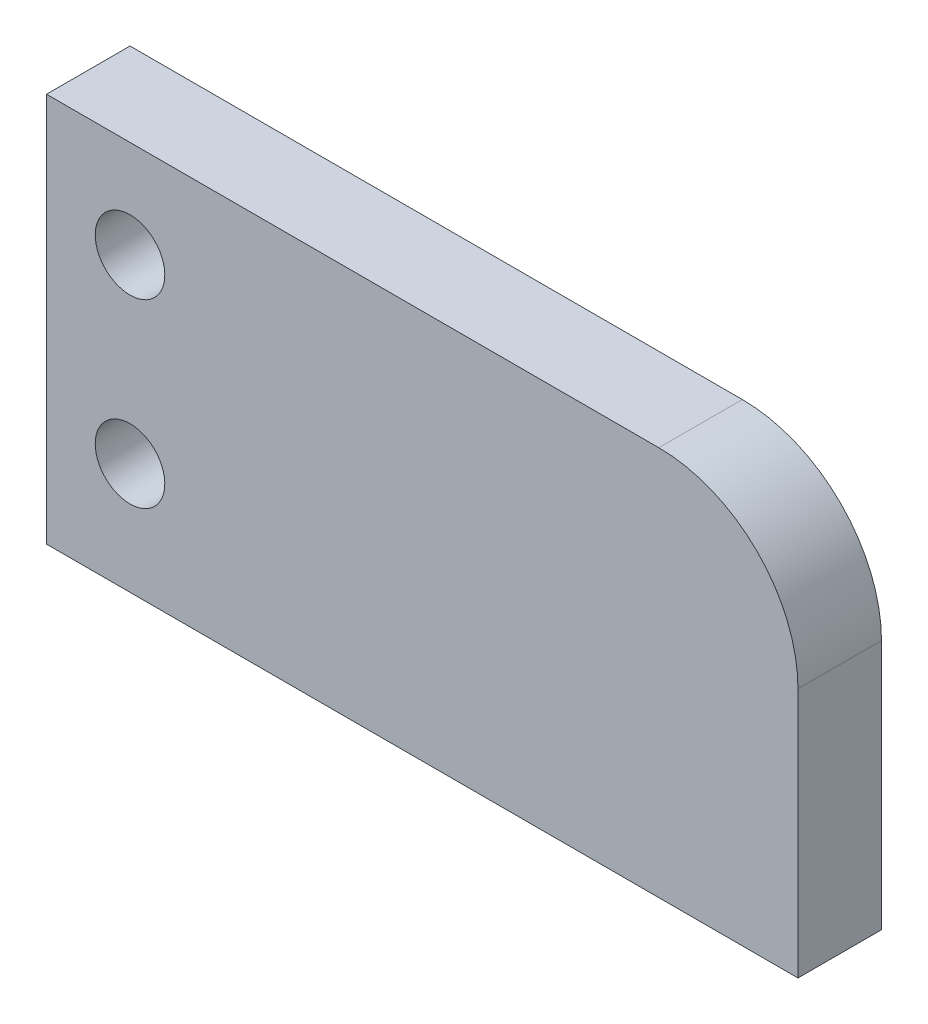
SolidWorks part; units mm, degrees
note: The reader was unsure of these and kept them because the rebuilt part matched: shared geometry of "Sketch2<3>".
ref_plane "Front Plane" through (0, 0, 0) normal (0, 0, 1) x (1, 0, 0)
ref_plane "Top Plane" through (0, 0, 0) normal (0, 1, 0) x (1, 0, 0)
ref_plane "Right Plane" through (0, 0, 0) normal (1, 0, 0) x (0, 0, -1)
sketch "Sketch1" plane through (0, 0, 0) normal (0, 0, 1) x (1, 0, 0)
  line L0 (0, 0) -> (0, 58)
  line L1 (0, 58) -> (19, 58)
  line L2 (19, 58) -> (19, 0)
  line L3 (19, 0) -> (0, 0)
  dimension "D1" = 58
  dimension "D2" = 19
extrude "Boss-Extrude1" add sketch "Sketch1" along normal blind 54
sketch "Sketch2" plane through (0, 0, 0) normal (-1, 0, 0) x (0, 0, 1)
  line L0 (0, 29) -> (27.5, 29)
  line L1 (0, 58) -> (0, 0) construction
  line L2 (27.5, 29) -> (54, 29)
  line L3 (54, 58) -> (54, 0) construction
  circle A0 centre (9.25, 29) radius 1.9
  circle A1 centre (45.75, 29) radius 1.9
  circle A2 centre (27.5, 29) radius 20
  circle A3 centre (27.5, 29) radius 15.5
  dimension "D4" = 3.8
  dimension "D5" = 3.8
  dimension "D6" = 31
  dimension "D7" = 40
  dimension "D1" = 27.5
  dimension "D2" = 18.25
  dimension "D3" = 18.25
extrude "Boss-Extrude2" add sketch "Sketch2<3>" against normal blind 50 contours A3 L0 A0 A2 A1 L2 | A1 A2 L2 | L2 A2 A1 | A3 L2 A1 A2 A0 L0 | A0 A2 L0 | L0 A2 A0
sketch "Sketch2<3>" plane through (0, 0, 0) normal (-1, 0, 0) x (0, 0, 1) same geometry as "Sketch2"
extrude "Cut-Extrude1" cut sketch "Sketch2" against normal blind 10 contours L0 A0 | L0 A0 | L2 A1 | L2 A1 | A2 L0 A0 | A2 A0 L0 | A2 A1 L2 | A2 L2 A1
fillet "Fillet1" radius 10 1 edges at (9.5, 0, 0)
sketch "Sketch3" plane through (0, 0, 0) normal (1, 0, 0) x (0, 0, -1)
  line L0 (0, 0) -> (0, 57)
  line L1 (0, 57) -> (0, 67)
  line L2 (0, 67) -> (-5, 67)
  line L3 (-5, 67) -> (-5, 0)
  line L4 (-54, 0) -> (-10, 0) construction
  line L5 (-5, 0) -> (0, 0)
  dimension "D1" = 57
  dimension "D2" = 5
  dimension "D3" = 10
extrude "Boss-Extrude3" add sketch "Sketch3" against normal blind 50
sketch "Sketch4" plane through (0, 0, 0) normal (0, 0, -1) x (-1, 0, 0)
  line L0 (0, 0) -> (0, 57)
  line L1 (0, 67) -> (0, 0) construction
  line L2 (0, 57) -> (14, 57)
  line L3 (0, 53) -> (50, 53)
  line L4 (50, 0) -> (50, 67) construction
  line L5 (50, 53) -> (50, 0)
  line L6 (50, 0) -> (0, 0)
  line L7 (17, 53) -> (17, 67)
  line L8 (50, 67) -> (0, 67) construction
  line L9 (17, 67) -> (50, 67)
  line L10 (50, 67) -> (50, 53)
  circle A0 centre (14, 57) radius 1.25
  circle A1 centre (14, 63.5) radius 1.25
  dimension "D2" = 2.5
  dimension "D3" = 2.5
  dimension "D1" = 57
  dimension "D4" = 6.5
  dimension "D5" = 14
  dimension "D6" = 53
  dimension "D7" = 3
extrude "Cut-Extrude2" cut sketch "Sketch4" against normal through all
sketch "Sketch5" plane through (0, 0, 0) normal (0, 0, -1) x (-1, 0, 0)
  line L0 (0, 67) -> (0, 53)
  line L1 (0, 53) -> (17, 53)
  line L2 (17, 53) -> (17, 67)
  line L3 (17, 67) -> (0, 67)
extrude "Cut-Extrude3" cut sketch "Sketch5" against normal blind 2
sketch "Sketch6" plane through (0, 58, 0) normal (0, 1, 0) x (1, 0, 0)
  line L0 (0, -5.5) -> (0, -1.5)
  line L1 (0, -54) -> (0, -5) construction
  line L2 (0, -5) -> (0, 0) construction
  line L3 (0, -1.5) -> (19, -1.5)
  line L4 (19, -54) -> (19, 0) construction
  line L5 (19, -1.5) -> (19, -5.5)
  line L6 (19, -47.5) -> (19, -7.5) construction
  line L7 (19, -5.5) -> (0, -5.5)
  line L8 (-17, -5) -> (0, -5) construction
  line L9 (-17, -2) -> (0, -2) construction
  dimension "D1" = 0.5
  dimension "D2" = 0.5
sketch "Sketch7" plane through (0, 58, 0) normal (0, 1, 0) x (1, 0, 0)
  line L0 (0, 0) -> (50, 0)
  line L1 (50, 0) -> (50, -57)
  line L2 (50, -57) -> (0, -57)
  line L3 (0, -57) -> (0, 0)
  dimension "D1" = 57
extrude "Cut-Extrude4" cut sketch "Sketch7" against normal through all
sketch "Sketch8" plane through (0, 0, 0) normal (1, 0, 0) x (0, 0, -1)
  line L0 (-5, 67) -> (-2, 67)
  line L1 (-2, 67) -> (-2, 53)
  line L2 (-2, 53) -> (-5, 53)
  line L3 (-5, 53) -> (-5, 67)
extrude "Boss-Extrude4" add sketch "Sketch8" along normal blind 10
fillet "Fillet2" radius 5 1 edges at (10, 67, 3.5)
